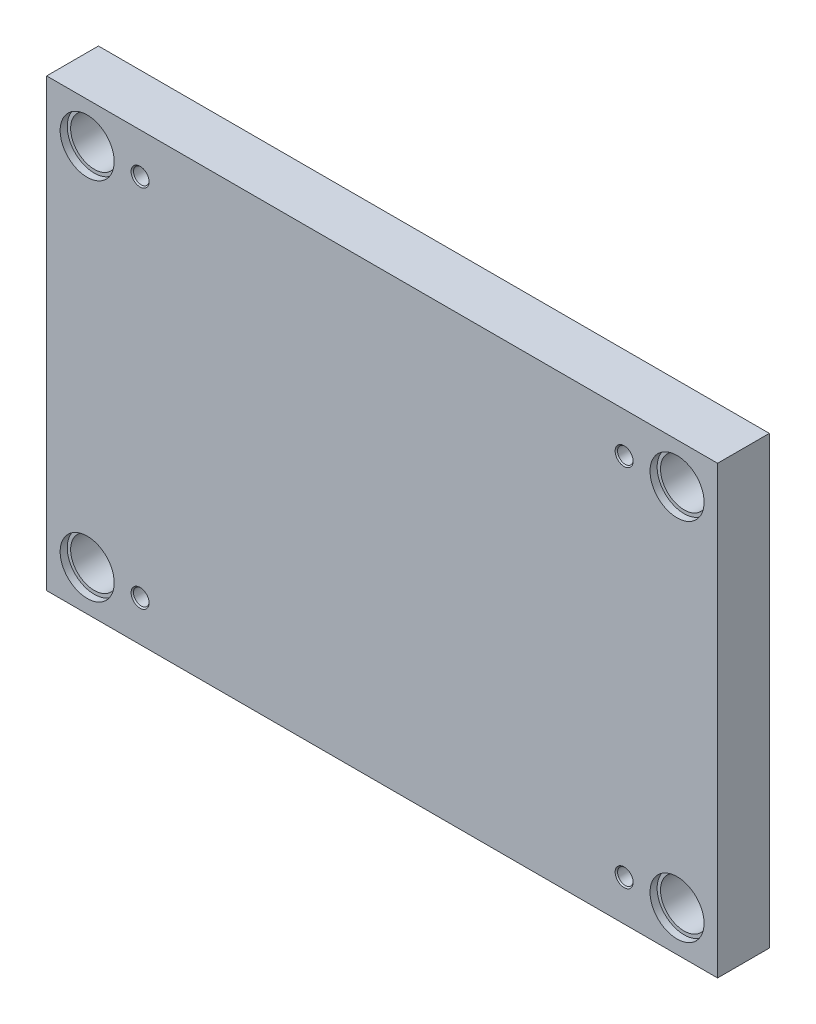
SolidWorks part; units mm, degrees
ref_plane "Płaszczyzna przednia" through (0, 0, 0) normal (0, 0, 1) x (1, 0, 0)
ref_plane "Płaszczyzna górna" through (0, 0, 0) normal (0, 1, 0) x (1, 0, 0)
ref_plane "Płaszczyzna prawa" through (0, 0, 0) normal (1, 0, 0) x (0, 0, -1)
sketch "Szkic1" plane through (0, 0, 0) normal (0, 0, 1) x (1, 0, 0)
  line L0 (-298, -198) -> (298, -198)
  line L1 (298, -198) -> (298, 198)
  line L2 (298, 198) -> (-298, 198)
  line L3 (-298, 198) -> (-298, -198)
extrude "Dodanie-wyciągnięcie1" add sketch "Szkic1" along normal blind 46
ref_plane "Płaszczyzna1" through (0, 0, 46) normal (0, 0, 1) x (1, 0, 0)
sketch "Szkic2" plane through (0, 0, 46) normal (0, 0, 1) x (1, 0, 0)
  circle A0 centre (262, 162) radius 21
extrude "Wytnij-wyciągnięcie1" cut sketch "Szkic2" against normal blind 46
sketch "Szkic3" plane through (0, 0, 46) normal (0, 0, 1) x (1, 0, 0)
  circle A0 centre (262, -162) radius 21
extrude "Wytnij-wyciągnięcie2" cut sketch "Szkic3" against normal blind 46
sketch "Szkic4" plane through (0, 0, 46) normal (0, 0, 1) x (1, 0, 0)
  circle A0 centre (-262, -162) radius 21
extrude "Wytnij-wyciągnięcie3" cut sketch "Szkic4" against normal blind 46
sketch "Szkic5" plane through (0, 0, 46) normal (0, 0, 1) x (1, 0, 0)
  circle A0 centre (-262, 162) radius 21
extrude "Wytnij-wyciągnięcie4" cut sketch "Szkic5" against normal blind 46
ref_plane "Płaszczyzna2" through (215, 0, 0) normal (1, 0, 0) x (0, 0, -1)
ref_plane "Płaszczyzna3" through (-215, 0, 0) normal (1, 0, 0) x (0, 0, -1)
sketch "Szkic6" plane through (0, 0, 46) normal (0, 0, 1) x (1, 0, 0)
  circle A0 centre (-262, 162) radius 24
extrude "Wytnij-wyciągnięcie5" cut sketch "Szkic6" against normal blind 6.3
sketch "Szkic7" plane through (0, 0, 46) normal (0, 0, 1) x (1, 0, 0)
  circle A0 centre (262, 162) radius 24
extrude "Wytnij-wyciągnięcie6" cut sketch "Szkic7" against normal blind 6.3
sketch "Szkic8" plane through (0, 0, 46) normal (0, 0, 1) x (1, 0, 0)
  circle A0 centre (-262, -162) radius 24
extrude "Wytnij-wyciągnięcie7" cut sketch "Szkic8" against normal blind 6.3
sketch "Szkic9" plane through (0, 0, 46) normal (0, 0, 1) x (1, 0, 0)
  circle A0 centre (262, -162) radius 24
extrude "Wytnij-wyciągnięcie8" cut sketch "Szkic9" against normal blind 6.3
sketch "Szkic10" plane through (-215, 0, 0) normal (1, 0, 0) x (0, 0, -1)
  line L0 (-46, 162) -> (-46, 170)
  line L1 (-46, 170) -> (-44.9175, 168.9175)
  line L2 (-44.9175, 168.9175) -> (-6, 168.9175)
  line L3 (-6, 168.9175) -> (-2.0062, 162)
  line L4 (-2.0062, 162) -> (-46, 162)
  line L5 (-2.0062, 162) -> (-46, 162) construction
revolve "Wycięcie-obrót1" cut sketch "Szkic10" angle 360 about L5 reverse direction yes
cosmetic thread "Oznaczenie gwintu1" parameters "D1"=30, "D2"=16
sketch "Szkic11" plane through (-215, 0, 0) normal (1, 0, 0) x (0, 0, -1)
  line L0 (-2.0062, -162) -> (-6, -168.9175)
  line L1 (-6, -168.9175) -> (-44.9175, -168.9175)
  line L2 (-44.9175, -168.9175) -> (-46, -170)
  line L3 (-46, -170) -> (-46, -162)
  line L4 (-46, -162) -> (-2.0062, -162)
  line L5 (-46, -162) -> (-2.0062, -162) construction
revolve "Wycięcie-obrót2" cut sketch "Szkic11" angle 360 about L5 reverse direction yes
cosmetic thread "Oznaczenie gwintu2" parameters "D1"=30, "D2"=16
sketch "Szkic12" plane through (215, 0, 0) normal (1, 0, 0) x (0, 0, -1)
  line L0 (-46, 162) -> (-46, 170)
  line L1 (-46, 170) -> (-44.9175, 168.9175)
  line L2 (-44.9175, 168.9175) -> (-6, 168.9175)
  line L3 (-6, 168.9175) -> (-2.0062, 162)
  line L4 (-2.0062, 162) -> (-46, 162)
  line L5 (-2.0062, 162) -> (-46, 162) construction
revolve "Wycięcie-obrót3" cut sketch "Szkic12" angle 360 about L5 reverse direction yes
cosmetic thread "Oznaczenie gwintu3" parameters "D1"=30, "D2"=16
sketch "Szkic13" plane through (215, 0, 0) normal (1, 0, 0) x (0, 0, -1)
  line L0 (-2.0062, -162) -> (-6, -168.9175)
  line L1 (-6, -168.9175) -> (-44.9175, -168.9175)
  line L2 (-44.9175, -168.9175) -> (-46, -170)
  line L3 (-46, -170) -> (-46, -162)
  line L4 (-46, -162) -> (-2.0062, -162)
  line L5 (-46, -162) -> (-2.0062, -162) construction
revolve "Wycięcie-obrót4" cut sketch "Szkic13" angle 360 about L5 reverse direction yes
cosmetic thread "Oznaczenie gwintu4" parameters "D1"=30, "D2"=16
ref_plane "Płaszczyzna4" through (0, 0, 46) normal (0, 0, 1) x (1, 0, 0)
ref_plane "Płaszczyzna5" through (0, 0, 46) normal (0, 0, 1) x (1, 0, 0)
ref_plane "IP2 XY" through (0, 0, 46) normal (0, 0, 1) x (1, 0, 0)
ref_plane "IP2 XZ" through (0, 162, 0) normal (0, -1, 0) x (-1, 0, 0)
ref_plane "IP2 YZ" through (-262, 0, 0) normal (1, 0, 0) x (0, 0, -1)
ref_axis "IP2 X" through (-80.9, 162, 46) along (1, 0, 0)
ref_axis "IP2 Y" through (-262, -50, 46) along (0, 1, 0)
ref_axis "IP2 Z" through (-262, 162, 80.9) along (0, 0, -1)
sketch3d "IP2"
  point P0 (-262, 162, 46)
ref_plane "IP3 XY" through (0, 0, 46) normal (0, 0, 1) x (1, 0, 0)
ref_plane "IP3 XZ" through (0, 162, 0) normal (0, -1, 0) x (-1, 0, 0)
ref_plane "IP3 YZ" through (262, 0, 0) normal (1, 0, 0) x (0, 0, -1)
ref_axis "IP3 X" through (-80.9, 162, 46) along (1, 0, 0)
ref_axis "IP3 Y" through (262, -50, 46) along (0, 1, 0)
ref_axis "IP3 Z" through (262, 162, 80.9) along (0, 0, -1)
sketch3d "IP3"
  point P0 (262, 162, 46)
ref_plane "IP4 XY" through (0, 0, 46) normal (0, 0, 1) x (1, 0, 0)
ref_plane "IP4 XZ" through (0, -162, 0) normal (0, -1, 0) x (-1, 0, 0)
ref_plane "IP4 YZ" through (-262, 0, 0) normal (1, 0, 0) x (0, 0, -1)
ref_axis "IP4 X" through (-80.9, -162, 46) along (1, 0, 0)
ref_axis "IP4 Y" through (-262, -50, 46) along (0, 1, 0)
ref_axis "IP4 Z" through (-262, -162, 80.9) along (0, 0, -1)
sketch3d "IP4"
  point P0 (-262, -162, 46)
ref_plane "IP5 XY" through (0, 0, 46) normal (0, 0, 1) x (1, 0, 0)
ref_plane "IP5 XZ" through (0, -162, 0) normal (0, -1, 0) x (-1, 0, 0)
ref_plane "IP5 YZ" through (262, 0, 0) normal (1, 0, 0) x (0, 0, -1)
ref_axis "IP5 X" through (-80.9, -162, 46) along (1, 0, 0)
ref_axis "IP5 Y" through (262, -50, 46) along (0, 1, 0)
ref_axis "IP5 Z" through (262, -162, 80.9) along (0, 0, -1)
sketch3d "IP5"
  point P0 (262, -162, 46)
ref_plane "IP1 XY" through (0, 0, 46) normal (0, 0, -1) x (-1, 0, 0)
ref_plane "IP1 XZ" through (0, 0, 0) normal (0, 1, 0) x (1, 0, 0)
ref_plane "IP1 YZ" through (0, 0, 0) normal (1, 0, 0) x (0, 0, -1)
ref_axis "IP1 X" through (-80.9, 0, 46) along (1, 0, 0)
ref_axis "IP1 Y" through (0, 50, 46) along (0, -1, 0)
ref_axis "IP1 Z" through (0, 0, -80.9) along (0, 0, 1)
sketch3d "IP1"
  point P0 (0, 0, 46)
